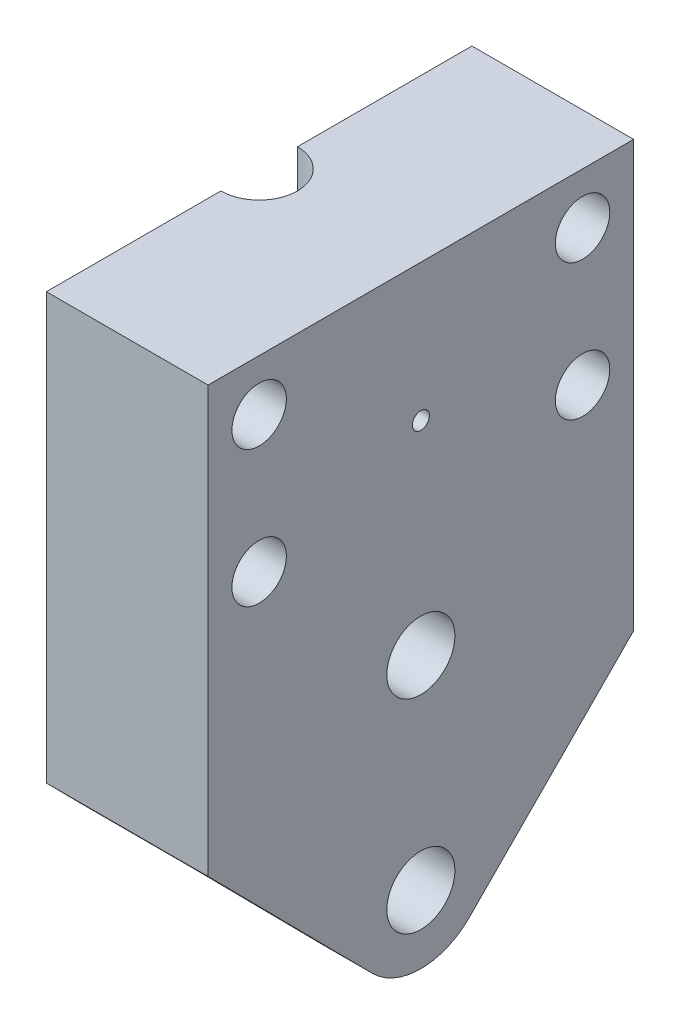
SolidWorks part; units mm, degrees
ref_plane "Front Plane" through (0, 0, 0) normal (0, 0, 1) x (1, 0, 0)
ref_plane "Top Plane" through (0, 0, 0) normal (0, 1, 0) x (1, 0, 0)
ref_plane "Right Plane" through (0, 0, 0) normal (1, 0, 0) x (0, 0, -1)
sketch "Sketch1" plane through (0, 0, 0) normal (1, 0, 0) x (0, 0, -1)
  line L0 (0, -11.95) -> (0, 11.95) construction
  line L9 (-12.5, -5) -> (12.5, -5) construction
  line L11 (12.5, -5) -> (12.5, 20)
  line L12 (12.5, 20) -> (-12.5, 20)
  line L13 (-12.5, -5) -> (-12.5, 20)
  line L16 (12.5, -5) -> (2.8147, -14.7921)
  line L17 (-12.5, -5) -> (-2.8147, -14.7921)
  circle A0 centre (0, 11.95) radius 0.5
  circle A1 centre (0, 0) radius 2
  circle A2 centre (0, -11.95) radius 2
  arc A4 (5.852, 8.1089) -> (-5.852, 8.1089) centre (0, 11.95) ccw
  arc A5 (8.8659, -4.6256) -> (5.852, 8.1089) centre (0, 0) ccw
  arc A6 (10.4259, -7.097) -> (8.8659, -4.6256) centre (0, -11.95) ccw
  arc A8 (-2.8147, -14.7921) -> (2.8147, -14.7921) centre (0, -11.95) ccw
  arc A9 (-8.8659, -4.6256) -> (-10.4259, -7.097) centre (0, -11.95) ccw
  arc A10 (-5.852, 8.1089) -> (-8.8659, -4.6256) centre (0, 0) ccw
  point P4 (0, 0)
  dimension "D2" = 1
  dimension "D3" = 4
  dimension "D4" = 25
  dimension "D7" = 7
  dimension "D8" = 10
  dimension "D9" = 20
  dimension "D6" = 6.95
  dimension "D5" = 4
  dimension "D11" = 11.5
  dimension "D1" = 25
  dimension "D10" = 9.6853
extrude "Boss-Extrude1" add sketch "Sketch1" along normal blind 9.5 contours A4 A10 A9 L17 A8 L16 A6 A5 A0 A1 A2 | A10 A4 A5 A6 L16 L11 L12 L13 L17 A9 region at (0, -5.7892, -11.2008) region at (0, -10.6586, -6.3312)
extrude "Cut-Extrude1" cut sketch "Sketch1<3>" along normal blind 6.5 contours A4 A10 A9 L17 A8 L16 A6 A5 A0 A1 A2 region at (0, -10.6586, -6.3312)
sketch "Sketch1<3>" plane through (0, 0, 0) normal (1, 0, 0) x (0, 0, -1) same geometry as "Sketch1"
sketch "Sketch4" plane through (0, 0, 0) normal (1, 0, 0) x (0, 0, -1)
  line L0 (4.899, 16.95) -> (-4.899, 16.95)
  arc A0 (4.899, 16.95) -> (-4.899, 16.95) centre (0, 11.95) ccw
  arc A1 (5.852, 8.1089) -> (-5.852, 8.1089) centre (0, 11.95) ccw construction
  dimension "D1" = 5
extrude "Boss-Extrude2" add sketch "Sketch4" along normal blind 3 from surface starting at face at (0, 3.4836, 0)
sketch "Sketch3" plane through (0, 0, 0) normal (0, 1, 0) x (1, 0, 0)
  circle A0 centre (0, 0) radius 2.25
  dimension "D1" = 4.5
extrude "Cut-Extrude2" cut sketch "Sketch3" against normal blind 6 from surface starting at face at (4.75, 20, 0)
sketch "Sketch5" plane through (0, 0, 0) normal (1, 0, 0) x (0, 0, -1)
  line L0 (-2.25, 20) -> (-12.5, 20) construction
  line L1 (-12.5, -5) -> (-12.5, 20) construction
  line L2 (12.5, -5) -> (12.5, 20) construction
  line L3 (12.5, 20) -> (2.25, 20) construction
  circle A0 centre (9.5, 9) radius 1.6
  circle A1 centre (-9.5, 9) radius 1.6
  circle A2 centre (-9.5, 17) radius 1.6
  circle A3 centre (9.5, 17) radius 1.6
  dimension "D1" = 3.2
  dimension "D2" = 11
  dimension "D3" = 3
  dimension "D5" = 3
  dimension "D4" = 3
extrude "Cut-Extrude3" cut sketch "Sketch5" along normal blind 10
